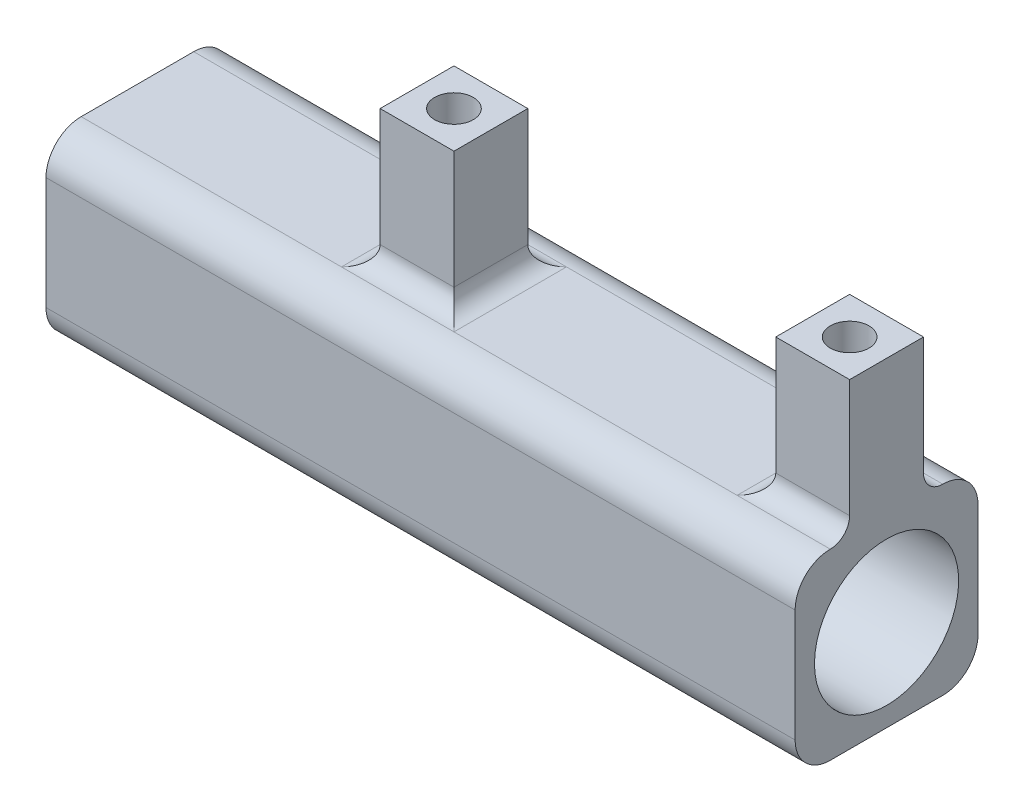
SolidWorks part; units mm, degrees
ref_plane "Front Plane" through (0, 0, 0) normal (0, 0, 1) x (1, 0, 0)
ref_plane "Top Plane" through (0, 0, 0) normal (0, 1, 0) x (1, 0, 0)
ref_plane "Right Plane" through (0, 0, 0) normal (1, 0, 0) x (0, 0, -1)
sketch "Sketch1" plane through (0, 0, 0) normal (0, 0, 1) x (1, 0, 0)
  line L1 (-53.25, 13) -> (53.25, 13)
  line L2 (-53.25, 13) -> (-53.25, -13)
  line L3 (-53.25, -13) -> (53.25, -13)
  line L4 (53.25, 13) -> (53.25, -13)
  line L7 (-13.5, 13) -> (-3, 13)
  line L8 (-13.5, 13) -> (-13.5, 32.5)
  line L9 (-13.5, 32.5) -> (-3, 32.5)
  line L10 (-3, 13) -> (-3, 32.5)
  line L11 (42.75, 13) -> (53.25, 13)
  line L12 (42.75, 13) -> (42.75, 32.5)
  line L13 (42.75, 32.5) -> (53.25, 32.5)
  line L14 (53.25, 13) -> (53.25, 32.5)
  point P0 (0, 0)
  point P10 (-8.25, 32.5)
  point P15 (-53.25, 0)
  point P24 (0, 13)
  dimension "D1" = 26
  dimension "D2" = 45
  dimension "D3" = 10.5
  dimension "D4" = 45.75
  dimension "D5" = 0
  dimension "D6" = 19.5
extrude "Boss-Extrude1" add sketch "Sketch1" along normal mid plane 26 contours L4 L1 L2 L3 region at (0, 0, 0)
extrude "Boss-Extrude2" add sketch "Sketch1<3>" along normal mid plane 10.5 contours L1 L10 L9 L8 | L1 L14 L13 L12 region at (-8.25, 22.75, 0) region at (48, 22.75, 0)
sketch "Sketch1<3>" plane through (0, 0, 0) normal (0, 0, 1) x (1, 0, 0) same geometry as "Sketch1"
sketch "Sketch2" plane through (-53.25, 0, 0) normal (-1, 0, 0) x (0, 0, 1)
  circle A0 centre (0, 0) radius 10.25
  dimension "D1" = 20.5
extrude "Cut-Extrude1" cut sketch "Sketch2" against normal through all
sketch "Sketch3" plane through (0, 32.5, 0) normal (0, 1, 0) x (1, 0, 0)
  circle A0 centre (-8.25, 0) radius 2.75
  circle A1 centre (48, 0) radius 2.75
  dimension "D1" = 5.5
extrude "Cut-Extrude2" cut sketch "Sketch3" against normal up to next
fillet "Fillet1" radius 5 4 edges at (0, -13, -13) (0, 13, -13) (0, -13, 13) (0, 13, 13)
fillet "Fillet4" radius 2.75 7 edges at (-13.5, 13, 0) (42.75, 13, 0) (-3, 13, 0) (48, 13, -5.25) (48, 13, 5.25) (-8.25, 13, 5.25) (-8.25, 13, -5.25)
